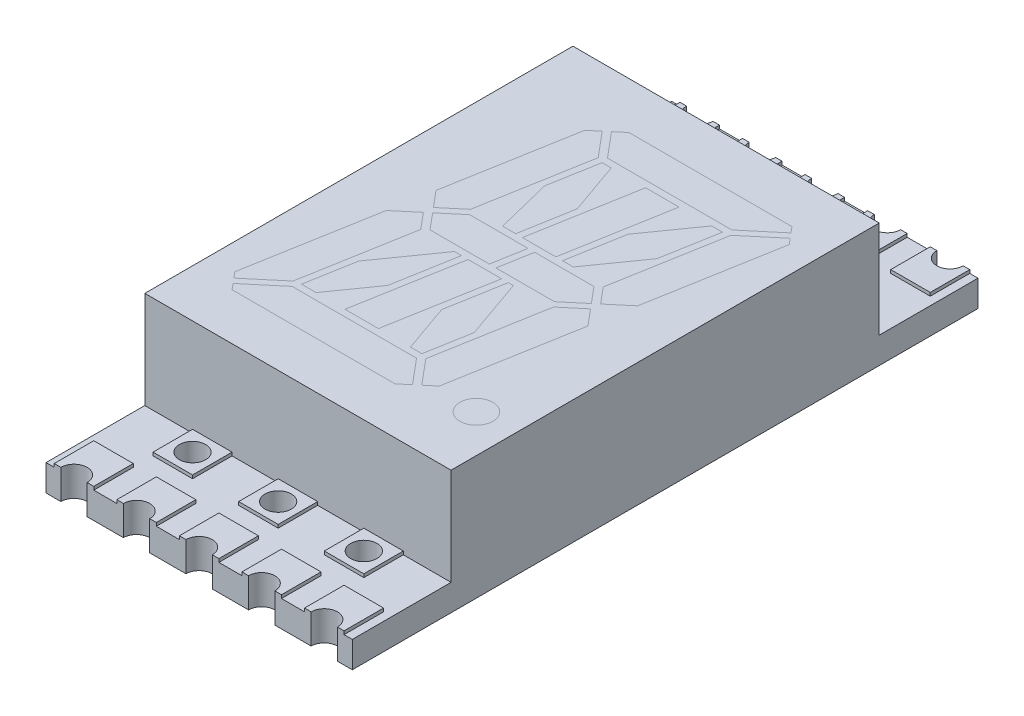
SolidWorks part; units mm, degrees
ref_plane "Спереди" through (0, 0, 0) normal (0, 0, 1) x (1, 0, 0)
ref_plane "Сверху" through (0, 0, 0) normal (0, 1, 0) x (1, 0, 0)
ref_plane "Справа" through (0, 0, 0) normal (1, 0, 0) x (0, 0, -1)
sketch "Эскиз1" plane through (0, 0, 0) normal (0, 1, 0) x (1, 0, 0)
  line L1 (-4.65, 9.5) -> (4.65, 9.5)
  line L2 (-4.65, 9.5) -> (-4.65, -9.5)
  line L3 (-4.65, -9.5) -> (4.65, -9.5)
  line L4 (4.65, 9.5) -> (4.65, -9.5)
  line L5 (-4.65, 9.5) -> (4.65, -9.5) construction
  line L6 (-4.65, -9.5) -> (4.65, 9.5) construction
  point P0 (0, 0)
  dimension "D1" = 9.3
  dimension "D2" = 19
extrude "Бобышка-Вытянуть1" add sketch "Эскиз1" along normal blind 0.8 contours L1 L4 L3 L2
sketch "Эскиз2" plane through (0, 0.8, 0) normal (0, 1, 0) x (1, 0, 0)
  line L0 (4.65, 9.5) -> (4.65, -9.5) construction
  line L1 (-4.65, 6.5) -> (4.65, 6.5)
  line L2 (-4.65, 6.5) -> (-4.65, -6.5)
  line L3 (-4.65, -6.5) -> (4.65, -6.5)
  line L4 (4.65, 6.5) -> (4.65, -6.5)
  line L5 (-4.65, 6.5) -> (4.65, -6.5) construction
  line L6 (-4.65, -6.5) -> (4.65, 6.5) construction
  point P0 (0, 0)
  dimension "D1" = 13
extrude "Бобышка-Вытянуть2" add sketch "Эскиз2" along normal blind 2.95
sketch "Эскиз3" plane through (0, 3.75, 0) normal (0, 1, 0) x (1, 0, 0)
  line L0 (0, 6.5) -> (0, -6.5) construction
  line L1 (4.65, 6.5) -> (-4.65, 6.5) construction
  line L2 (-4.65, -6.5) -> (4.65, -6.5) construction
  line L3 (-2.1505, 5.08) -> (3.942, 5.08) construction
  line L4 (-4.65, 6.5) -> (-4.65, -6.5) construction
  line L5 (-4.65, 0) -> (4.65, 0) construction
  line L6 (4.65, -6.5) -> (4.65, 6.5) construction
  line L7 (-2.1505, 5.08) -> (-3.942, -5.08) construction
  line L8 (3.942, 5.08) -> (2.1505, -5.08) construction
  line L9 (-3.942, -5.08) -> (2.1505, -5.08) construction
  line L10 (-2.1505, 5.08) -> (2.1505, -5.08) construction
  line L11 (-3.942, -5.08) -> (3.942, 5.08) construction
  point P6 (0, 0)
  point P17 (3.5, -4.58)
  dimension "D1" = 10.16
  dimension "D2" = 6
  dimension "D3" = 80
  dimension "D4" = 3.5
  dimension "D5" = 0.5
sketch "Эскиз6" plane through (0, 3.75, 0) normal (0, 1, 0) x (1, 0, 0)
  line L4 (-1.3114, 4.08) -> (-2.7503, -4.08) construction
  line L5 (-1.3114, 4.08) -> (2.7503, 4.08) construction
  line L6 (-2.7503, -4.08) -> (1.3114, -4.08) construction
  line L7 (2.7503, 4.08) -> (1.3114, -4.08) construction
  line L8 (4.65, -6.5) -> (4.65, 6.5)
  line L9 (4.65, 6.5) -> (-4.65, 6.5)
  line L10 (-4.65, 6.5) -> (-4.65, -6.5)
  line L11 (-4.65, -6.5) -> (4.65, -6.5)
  line L12 (4.65, -6.5) -> (4.65, 6.5)
  line L13 (4.65, 6.5) -> (-4.65, 6.5)
  line L14 (-4.65, 6.5) -> (-4.65, -6.5)
  line L15 (-4.65, -6.5) -> (4.65, -6.5)
  line L16 (3.942, 5.08) -> (2.1505, -5.08) construction
  line L17 (-2.1505, 5.08) -> (3.942, 5.08) construction
  line L18 (-3.942, -5.08) -> (2.1505, -5.08) construction
  line L19 (-2.1505, 5.08) -> (-3.942, -5.08) construction
  line L20 (-4.65, 0) -> (4.65, 0) construction
  line L21 (0.8957, 5.08) -> (-0.8957, -5.08) construction
  point P14 (3.0463, 0)
  point P15 (2.0309, 0)
  point P16 (-3.0463, 0)
  point P17 (-2.0309, 0)
  dimension "D2" = 1
  dimension "D3" = 1
  dimension "D4" = 1
  dimension "D5" = 1
  dimension "D1" = 0
sketch "Эскиз8" plane through (0, 3.75, 0) normal (0, 1, 0) x (1, 0, 0)
  line L0 (-1.3114, 4.08) -> (-2.1505, 5.08)
  line L1 (2.7503, 4.08) -> (3.942, 5.08)
  line L2 (2.107, 0.4316) -> (2.9702, -0.4316) construction
  line L3 (1.3114, -4.08) -> (2.1505, -5.08)
  line L4 (1.9222, -0.6164) -> (3.155, 0.6164) construction
  line L5 (-2.7503, -4.08) -> (-3.942, -5.08)
  line L6 (-1.2731, 4.1121) -> (-2.1122, 5.1121) construction
  line L7 (2.7824, 4.0417) -> (3.9742, 5.0417) construction
  line L8 (-2.9702, 0.4316) -> (-2.107, -0.4316) construction
  line L9 (-2.1505, 5.08) -> (3.942, 5.08) construction
  line L10 (-3.155, -0.6164) -> (-1.9222, 0.6164) construction
  line L11 (-2.0309, 0) -> (-3.0463, 0) construction
  line L12 (-2.1505, 5.08) -> (-3.942, -5.08) construction
  line L13 (-2.0309, 0.05) -> (-3.0463, 0.05) construction
  line L14 (2.0309, -0.05) -> (3.0463, -0.05) construction
  line L15 (2.0309, 0) -> (3.0463, 0) construction
  line L16 (1.2731, -4.1121) -> (2.1122, -5.1121) construction
  line L17 (3.942, 5.08) -> (2.1505, -5.08) construction
  line L18 (-2.7824, -4.0417) -> (-3.9742, -5.0417) construction
  line L19 (-1.3497, 4.0479) -> (-2.1888, 5.0479) construction
  line L20 (2.7181, 4.1183) -> (3.9099, 5.1183) construction
  line L21 (-4.65, 0) -> (4.65, 0) construction
  line L22 (-2.0309, -0.05) -> (-3.0463, -0.05) construction
  line L23 (2.0309, 0.05) -> (3.0463, 0.05) construction
  line L24 (1.3497, -4.0479) -> (2.1888, -5.0479) construction
  line L25 (2.7503, 4.08) -> (1.3114, -4.08) construction
  line L26 (-2.7181, -4.1183) -> (-3.9099, -5.1183) construction
  line L27 (-2.2593, 4.463) -> (-1.524, 5.08)
  line L28 (3.2529, 5.08) -> (3.8224, 4.4014)
  line L29 (-3.8224, -4.4014) -> (-3.2529, -5.08)
  line L30 (-1.3114, 4.08) -> (-2.7503, -4.08) construction
  line L31 (1.524, -5.08) -> (2.2593, -4.463)
  line L32 (-3.0055, 0.3963) -> (-2.1423, -0.467) construction
  line L33 (-3.1196, -0.6518) -> (-1.8868, 0.581) construction
  line L34 (2.0716, 0.3963) -> (2.9348, -0.467) construction
  line L35 (1.9575, -0.6518) -> (3.1903, 0.581) construction
  line L36 (-2.9348, 0.467) -> (-2.0716, -0.3963) construction
  line L37 (-3.1903, -0.581) -> (-1.9575, 0.6518) construction
  line L38 (2.1423, 0.467) -> (3.0055, -0.3963) construction
  line L39 (1.8868, -0.581) -> (3.1196, 0.6518) construction
  line L40 (-3.942, -5.08) -> (2.1505, -5.08) construction
  line L41 (-2.3186, 0.5) -> (2.4038, 0.5) construction
  line L43 (2.4038, -0.5) -> (-2.5616, -0.5) construction
  point P19 (2.5386, 0)
  point P21 (-2.5386, 0)
  point P70 (-1.731, 4.58)
  point P73 (3.3461, 4.58)
  point P76 (-3.3461, -4.58)
  point P79 (1.731, -4.58)
  dimension "D3" = 0.25
  dimension "D4" = 0.25
  dimension "D5" = 0.25
  dimension "D6" = 0.25
  dimension "D7" = 45
  dimension "D10" = 1
  dimension "D11" = 0.5
  dimension "D1" = 0.05
  dimension "D8" = 0.05
  dimension "D9" = 0.05
sketch "Эскиз10" plane through (0, 3.75, 0) normal (0, 1, 0) x (1, 0, 0)
  line L0 (-2.9596, 0.4917) -> (-2.5386, 0.0707)
  line L1 (-2.9348, 0.467) -> (-2.0716, -0.3963) construction
  line L2 (-3.1903, -0.581) -> (-1.9575, 0.6518) construction
  line L3 (-2.5386, 0.0707) -> (-1.907, 0.7022)
  line L4 (-1.907, 0.7022) -> (-1.3228, 4.0157)
  line L5 (-1.3497, 4.0479) -> (-2.1888, 5.0479) construction
  line L6 (-1.3228, 4.0157) -> (-1.93, 4.7394)
  line L7 (-2.2593, 4.463) -> (-1.524, 5.08) construction
  line L8 (-1.93, 4.7394) -> (-2.2593, 4.463)
  line L9 (-2.2593, 4.463) -> (-2.9596, 0.4917)
  line L10 (-2.1505, 5.08) -> (-3.942, -5.08) construction
  line L11 (-1.3114, 4.08) -> (-2.7503, -4.08) construction
  line L12 (2.1176, 0.4917) -> (2.5386, 0.0707)
  line L13 (2.5386, 0.0707) -> (3.1701, 0.7022)
  line L14 (3.1701, 0.7022) -> (3.8224, 4.4014)
  line L15 (3.8224, 4.4014) -> (3.5698, 4.7024)
  line L16 (3.5698, 4.7024) -> (2.7368, 4.0034)
  line L17 (2.7368, 4.0034) -> (2.1176, 0.4917)
  line L18 (-3.8224, -4.4014) -> (-3.5698, -4.7024)
  line L19 (2.1423, 0.467) -> (3.0055, -0.3963) construction
  line L20 (3.942, 5.08) -> (2.1505, -5.08) construction
  line L21 (2.7503, 4.08) -> (1.3114, -4.08) construction
  line L22 (1.8868, -0.581) -> (3.1196, 0.6518) construction
  line L23 (3.2529, 5.08) -> (3.8224, 4.4014) construction
  line L24 (2.7824, 4.0417) -> (3.9742, 5.0417) construction
  line L25 (-3.5698, -4.7024) -> (-2.7368, -4.0034)
  line L26 (-2.7368, -4.0034) -> (-2.1176, -0.4917)
  line L27 (-2.1176, -0.4917) -> (-2.5386, -0.0707)
  line L28 (-2.5386, -0.0707) -> (-3.1701, -0.7022)
  line L29 (-3.1701, -0.7022) -> (-3.8224, -4.4014)
  line L30 (-3.0055, 0.3963) -> (-2.1423, -0.467) construction
  line L31 (-3.1196, -0.6518) -> (-1.8868, 0.581) construction
  line L32 (-3.8224, -4.4014) -> (-3.2529, -5.08) construction
  line L33 (-2.7824, -4.0417) -> (-3.9742, -5.0417) construction
  line L34 (-3.2529, -5.08) -> (1.524, -5.08)
  line L35 (1.524, -5.08) -> (1.8534, -4.8037)
  line L36 (1.8534, -4.8037) -> (1.2462, -4.08)
  line L37 (1.2462, -4.08) -> (-2.6725, -4.08)
  line L38 (-2.6725, -4.08) -> (-3.5055, -4.779)
  line L39 (-3.5055, -4.779) -> (-3.2529, -5.08)
  line L40 (-2.7181, -4.1183) -> (-3.9099, -5.1183) construction
  line L41 (-2.7503, -4.08) -> (1.3114, -4.08) construction
  line L42 (-1.524, 5.08) -> (-1.8534, 4.8037)
  line L43 (1.2731, -4.1121) -> (2.1122, -5.1121) construction
  line L44 (1.524, -5.08) -> (2.2593, -4.463) construction
  line L45 (1.3228, -4.0157) -> (1.93, -4.7394)
  line L46 (1.93, -4.7394) -> (2.2593, -4.463)
  line L47 (2.2593, -4.463) -> (2.9596, -0.4917)
  line L48 (2.9596, -0.4917) -> (2.5386, -0.0707)
  line L49 (2.5386, -0.0707) -> (1.907, -0.7022)
  line L50 (1.907, -0.7022) -> (1.3228, -4.0157)
  line L51 (1.9575, -0.6518) -> (3.1903, 0.581) construction
  line L52 (2.0716, 0.3963) -> (2.9348, -0.467) construction
  line L53 (1.3497, -4.0479) -> (2.1888, -5.0479) construction
  line L54 (-1.8534, 4.8037) -> (-1.2462, 4.08)
  line L55 (-1.2462, 4.08) -> (2.6725, 4.08)
  line L56 (2.6725, 4.08) -> (3.5055, 4.779)
  line L57 (3.5055, 4.779) -> (3.2529, 5.08)
  line L58 (3.2529, 5.08) -> (-1.524, 5.08)
  line L59 (-1.2731, 4.1121) -> (-2.1122, 5.1121) construction
  line L60 (-1.3114, 4.08) -> (2.7503, 4.08) construction
  line L61 (2.7181, 4.1183) -> (3.9099, 5.1183) construction
  line L62 (-1.9679, 0.5) -> (-2.4679, 0)
  line L63 (-2.4679, 0) -> (-1.9679, -0.5)
  line L64 (-1.9679, -0.5) -> (1.9373, -0.5306)
  line L65 (1.9373, -0.5306) -> (2.4679, 0)
  line L66 (2.4679, 0) -> (1.9679, 0.5)
  line L67 (1.9679, 0.5) -> (-1.9679, 0.5)
  line L68 (-4.65, 0) -> (4.65, 0) construction
  line L69 (2.4038, -0.5) -> (-2.5616, -0.5) construction
  line L70 (-2.3186, 0.5) -> (2.4038, 0.5) construction
sketch "Эскиз11" plane through (0, 3.75, 0) normal (0, 1, 0) x (1, 0, 0)
  line L0 (2.7503, 4.08) -> (3.942, 5.08) construction
  line L1 (-2.119, -0.5) -> (1.9427, -0.5) construction
  line L2 (-1.3114, 4.08) -> (-2.7503, -4.08) construction
  line L3 (-2.1505, 5.08) -> (-1.3114, 4.08) construction
  line L4 (2.7503, 4.08) -> (1.3114, -4.08) construction
  line L5 (-4.65, 0) -> (4.65, 0) construction
  line L6 (-2.7503, -4.08) -> (-3.6356, -4.8229) construction
  line L7 (-1.9427, 0.5) -> (2.119, 0.5) construction
  line L8 (0.1243, 0.7052) -> (-0.0912, -0.5174) construction
  line L9 (-1.97, 4.7093) -> (-1.3341, 3.9514) construction
  line L10 (2.119, 0.5) -> (3.0121, -0.5643) construction
  line L11 (-2.1505, 5.08) -> (3.942, 5.08) construction
  line L12 (3.942, 5.08) -> (2.1505, -5.08) construction
  line L13 (2.1505, -5.08) -> (-3.942, -5.08) construction
  line L14 (-3.942, -5.08) -> (-2.1505, 5.08) construction
  line L15 (-1.3114, 4.08) -> (2.7503, 4.08) construction
  line L16 (2.7503, 4.08) -> (1.3114, -4.08) construction
  line L17 (1.3114, -4.08) -> (-2.7503, -4.08) construction
  line L18 (-2.7503, -4.08) -> (-1.3114, 4.08) construction
  line L19 (2.0309, 0) -> (3.0463, 0) construction
  line L20 (-2.9581, 0.5) -> (-2.119, -0.5) construction
  line L21 (1.9427, -0.5) -> (3.2257, 0.5766) construction
  line L22 (-3.0463, 0) -> (-2.0309, 0) construction
  line L23 (-3.1344, -0.5) -> (-1.9427, 0.5) construction
  line L24 (1.3114, -4.08) -> (1.8934, -4.7736) construction
  line L25 (-2.9808, 0.3714) -> (-2.1417, -0.6286) construction
  line L26 (-3.1615, -0.6532) -> (-1.7871, 0.5) construction
  line L27 (-2.7233, -3.9268) -> (-3.6999, -4.7463) construction
  line L28 (1.1809, -4.08) -> (1.8168, -4.8379) construction
  line L29 (1.9157, -0.6532) -> (3.29, 0.5) construction
  line L30 (1.9885, 0.5) -> (2.9354, -0.6286) construction
  line L31 (2.7233, 3.9268) -> (3.6999, 4.7463) construction
  line L32 (-1.8168, 4.8379) -> (-1.1809, 4.08) construction
  line L33 (-2.9354, 0.6286) -> (-1.9885, -0.5) construction
  line L34 (-3.1074, -0.3468) -> (-1.9157, 0.6532) construction
  line L35 (-2.5947, -4.08) -> (-3.5713, -4.8995) construction
  line L36 (1.3341, -3.9514) -> (1.97, -4.7093) construction
  line L37 (1.7871, -0.5) -> (3.1615, 0.6532) construction
  line L38 (2.1417, 0.6286) -> (3.0887, -0.5) construction
  line L39 (2.5947, 4.08) -> (3.5713, 4.8995) construction
  line L40 (-2.2586, 4.4672) -> (-1.5282, 5.08) construction
  line L41 (3.4199, 5.08) -> (3.8513, 4.5658) construction
  line L42 (1.5282, -5.08) -> (2.2586, -4.4672) construction
  line L43 (-2.4124, 5.5477) -> (-1.1809, 4.08) construction
  line L44 (-3.8513, -4.5658) -> (-3.4199, -5.08) construction
  line L45 (-2.5656, 5.4191) -> (-1.3341, 3.9514) construction
  line L46 (2.1182, 3.6802) -> (3.8777, 5.1566) construction
  line L47 (2.2468, 3.527) -> (4.0063, 5.0034) construction
  line L48 (-3.7801, -0.9113) -> (-2.007, 0.5766) construction
  line L49 (-3.6516, -1.0645) -> (-1.8784, 0.4234) construction
  line L50 (-3.2753, 0.7224) -> (-2.1956, -0.5643) construction
  line L51 (-3.1221, 0.851) -> (-2.0424, -0.4357) construction
  line L52 (-2.3638, -3.6252) -> (-3.6999, -4.7463) construction
  line L53 (-2.2353, -3.7784) -> (-3.5713, -4.8995) construction
  line L54 (0.6343, -3.1175) -> (1.97, -4.7093) construction
  line L55 (0.4811, -3.246) -> (1.8168, -4.8379) construction
  line L56 (2.0029, 0.794) -> (3.0887, -0.5) construction
  line L57 (1.8496, 0.6655) -> (2.9354, -0.6286) construction
  line L58 (1.4413, -0.7902) -> (3.1615, 0.6532) construction
  line L59 (1.5699, -0.9434) -> (3.29, 0.5) construction
  line L60 (-3.7159, -0.9879) -> (-1.9427, 0.5) construction
  line L61 (-0.0134, 0.5) -> (-0.1897, -0.5) construction
  line L62 (0.1897, 0.5) -> (0.0134, -0.5) construction
  line L63 (0.0259, 0.7226) -> (-0.1897, -0.5) construction
  line L64 (0.2228, 0.6878) -> (0.0073, -0.5347) construction
  line L65 (0.5577, -3.1818) -> (1.8934, -4.7736) construction
  line L66 (2.1825, 3.6036) -> (3.942, 5.08) construction
  line L67 (-2.489, 5.4834) -> (-1.2575, 4.0157) construction
  line L68 (-3.1987, 0.7867) -> (-2.119, -0.5) construction
  line L69 (1.9262, 0.7297) -> (3.0121, -0.5643) construction
  line L70 (1.5056, -0.8668) -> (3.2257, 0.5766) construction
  line L71 (-2.2995, -3.7018) -> (-3.6356, -4.8229) construction
  point P34 (2.5386, 0)
  point P43 (-2.5386, 0)
  point P47 (0.0882, 0.5)
  point P49 (-0.0882, -0.5)
  dimension "D1" = 1
  dimension "D2" = 0.5
  dimension "D5" = 0.4
  dimension "D6" = 0.4
  dimension "D7" = 0.4
  dimension "D8" = 0.4
  dimension "D3" = 0.1
  dimension "D4" = 0.1
sketch "Эскиз13" plane through (0, 3.75, 0) normal (0, 1, 0) x (1, 0, 0)
  line L0 (-2.9354, 0.6286) -> (-2.2586, 4.4672)
  line L1 (-2.2586, 4.4672) -> (-1.97, 4.7093)
  line L2 (-1.97, 4.7093) -> (-1.3341, 3.9514)
  line L3 (-1.3341, 3.9514) -> (-1.9157, 0.6532)
  line L4 (-1.9157, 0.6532) -> (-2.5262, 0.1409)
  line L5 (-2.9354, 0.6286) -> (-1.9885, -0.5) construction
  line L6 (-3.1074, -0.3468) -> (-1.9157, 0.6532) construction
  line L7 (-2.5262, 0.1409) -> (-2.9354, 0.6286)
  line L8 (-3.1615, -0.6532) -> (-2.5509, -0.1409)
  line L9 (-2.9808, 0.3714) -> (-2.1417, -0.6286) construction
  line L10 (-3.1615, -0.6532) -> (-1.7871, 0.5) construction
  line L11 (-2.5509, -0.1409) -> (-2.1417, -0.6286)
  line L12 (-2.1417, -0.6286) -> (-2.7233, -3.9268)
  line L13 (-2.7233, -3.9268) -> (-3.6999, -4.7463)
  line L14 (-3.6999, -4.7463) -> (-3.8513, -4.5658)
  line L15 (-3.8513, -4.5658) -> (-3.1615, -0.6532)
  line L16 (-3.5713, -4.8995) -> (-2.5947, -4.08)
  line L17 (-2.5947, -4.08) -> (1.1809, -4.08)
  line L18 (1.1809, -4.08) -> (1.8168, -4.8379)
  line L19 (1.8168, -4.8379) -> (1.5282, -5.08)
  line L20 (1.5282, -5.08) -> (-3.4199, -5.08)
  line L21 (-3.4199, -5.08) -> (-3.5713, -4.8995)
  line L22 (1.9157, -0.6532) -> (2.5262, -0.1409)
  line L23 (1.9157, -0.6532) -> (3.29, 0.5) construction
  line L24 (1.9885, 0.5) -> (2.9354, -0.6286) construction
  line L25 (2.5262, -0.1409) -> (2.9354, -0.6286)
  line L26 (2.9354, -0.6286) -> (2.2586, -4.4672)
  line L27 (2.2586, -4.4672) -> (1.97, -4.7093)
  line L28 (1.97, -4.7093) -> (1.3341, -3.9514)
  line L29 (1.3341, -3.9514) -> (1.9157, -0.6532)
  line L30 (2.1417, 0.6286) -> (2.5509, 0.1409)
  line L31 (1.7871, -0.5) -> (3.1615, 0.6532) construction
  line L32 (2.1417, 0.6286) -> (3.0887, -0.5) construction
  line L33 (2.5509, 0.1409) -> (3.1615, 0.6532)
  line L34 (3.1615, 0.6532) -> (3.8513, 4.5658)
  line L35 (3.8513, 4.5658) -> (3.6999, 4.7463)
  line L36 (3.6999, 4.7463) -> (2.7233, 3.9268)
  line L37 (2.7233, 3.9268) -> (2.1417, 0.6286)
  line L38 (-1.8168, 4.8379) -> (-1.5282, 5.08)
  line L39 (-1.5282, 5.08) -> (3.4199, 5.08)
  line L40 (3.4199, 5.08) -> (3.5713, 4.8995)
  line L41 (3.5713, 4.8995) -> (2.5947, 4.08)
  line L42 (2.5947, 4.08) -> (-1.1809, 4.08)
  line L43 (-1.1809, 4.08) -> (-1.8168, 4.8379)
  line L44 (-1.9885, -0.5) -> (-0.1897, -0.5)
  line L45 (-0.1897, -0.5) -> (-0.0134, 0.5)
  line L46 (-0.0134, 0.5) -> (-1.7871, 0.5)
  line L47 (-1.7871, 0.5) -> (-2.3977, -0.0123)
  line L48 (-2.3977, -0.0123) -> (-1.9885, -0.5)
  line L49 (0.1897, 0.5) -> (1.9885, 0.5)
  line L50 (1.9885, 0.5) -> (2.3977, 0.0123)
  line L51 (2.3977, 0.0123) -> (1.7871, -0.5)
  line L52 (1.7871, -0.5) -> (0.0134, -0.5)
  line L53 (0.0134, -0.5) -> (0.1897, 0.5)
sketch "Эскиз14" plane through (0, 3.75, 0) normal (0, 1, 0) x (1, 0, 0)
  line L0 (-1.8175, 5.08) -> (1.748, -5.08) construction
  line L1 (0.8957, 5.08) -> (-0.8957, -5.08) construction
  line L2 (-2.1505, 5.08) -> (3.942, 5.08) construction
  line L3 (-3.5295, -5.08) -> (3.6422, 5.08) construction
  line L4 (2.1505, -5.08) -> (-3.942, -5.08) construction
  line L6 (-1.5282, 5.08) -> (3.4199, 5.08) construction
  line L7 (-1.5582, 0.5) -> (1.9885, 0.5) construction
  line L8 (-1.1436, 3.88) -> (-1.7043, 0.7) construction
  line L9 (2.7503, 4.08) -> (1.3114, -4.08) construction
  line L10 (2.1536, 0.6964) -> (2.6916, 3.7472)
  line L11 (2.5119, 3.88) -> (-1.1436, 3.88) construction
  line L12 (-1.3114, 4.08) -> (2.7503, 4.08) construction
  line L13 (2.1536, 4.08) -> (-1.1436, 4.08) construction
  line L14 (1.9512, 0.7) -> (2.5119, 3.88) construction
  line L15 (-2.7503, -4.08) -> (-1.3114, 4.08) construction
  line L16 (-1.3701, 3.7472) -> (-1.9013, 0.7347) construction
  line L17 (-1.9427, 0.5) -> (2.119, 0.5) construction
  line L18 (-1.7043, 0.7) -> (1.9885, 0.7) construction
  line L19 (1.4695, -0.7) -> (-1.6378, -0.7) construction
  line L20 (1.3114, -4.08) -> (-2.7503, -4.08) construction
  line L21 (1.3569, -3.822) -> (1.8699, -0.9131) construction
  line L22 (-1.9949, -0.9478) -> (-2.5119, -3.88) construction
  line L23 (1.4695, -0.5) -> (-1.6378, -0.5) construction
  line L24 (-2.5119, -3.88) -> (1.1436, -3.88) construction
  line L25 (-2.1919, -0.9131) -> (-2.6711, -3.6308) construction
  line L26 (-2.4334, -4.08) -> (0.7693, -4.08) construction
  line L27 (-2.119, -0.5) -> (1.9427, -0.5) construction
  line L28 (1.1436, -3.88) -> (1.6729, -0.8783) construction
  line L29 (1.9567, 0.7311) -> (2.4946, 3.7819) construction
  line L30 (2.1536, 3.88) -> (-1.1436, 3.88) construction
  line L31 (-1.1732, 3.7125) -> (-1.7043, 0.7) construction
  line L32 (-1.5582, 0.7) -> (1.9885, 0.7) construction
  line L33 (1.16, -3.7873) -> (1.6729, -0.8783) construction
  line L34 (-2.4334, -3.88) -> (0.7693, -3.88) construction
  line L35 (-1.9949, -0.9478) -> (-2.4741, -3.6655) construction
  dimension "D1" = 0.2
  dimension "D2" = 0.2
sketch "Эскиз16" plane through (0, 3.75, 0) normal (0, 1, 0) x (1, 0, 0)
  line L0 (-0.1234, -0.7) -> (-0.6841, -3.88) construction
  line L2 (-2.5119, -3.88) -> (1.1436, -3.88) construction
  line L3 (0.8957, 5.08) -> (-0.8957, -5.08) construction
  line L4 (1.4695, -0.7) -> (-1.6378, -0.7) construction
  line L5 (0.6841, 3.88) -> (0.1234, 0.7) construction
  line L6 (2.5119, 3.88) -> (-1.1436, 3.88) construction
  line L7 (-1.7043, 0.7) -> (1.9885, 0.7) construction
  line L8 (0.1764, 3.88) -> (-0.3843, 0.7) construction
  line L9 (-0.6311, -0.7) -> (-1.1766, -3.7932) construction
  line L10 (1.1919, 3.88) -> (0.6311, 0.7) construction
  line L11 (0.3843, -0.7) -> (-0.1917, -3.9668) construction
  line L12 (0.1917, 3.9668) -> (-0.369, 0.7868) construction
  line L13 (1.1766, 3.7932) -> (0.6158, 0.6132) construction
  line L14 (-0.6158, -0.6132) -> (-1.1766, -3.7932) construction
  line L15 (0.369, -0.7868) -> (-0.1917, -3.9668) construction
  dimension "D1" = 0.5
  dimension "D2" = 0.5
sketch "Эскиз17" plane through (0, 3.75, 0) normal (0, 1, 0) x (1, 0, 0)
  line L0 (-0.3843, 0.7) -> (0.6311, 0.7)
  line L1 (-0.3843, 0.7) -> (0.1764, 3.88)
  line L2 (0.6311, 0.7) -> (1.1919, 3.88)
  line L3 (0.1764, 3.88) -> (1.1919, 3.88)
  line L4 (-0.6311, -0.7) -> (-1.1919, -3.88)
  line L5 (-0.6311, -0.7) -> (0.3843, -0.7)
  line L6 (-1.1919, -3.88) -> (-0.1764, -3.88)
  line L7 (0.3843, -0.7) -> (-0.1764, -3.88)
  line L8 (-2.5119, -3.88) -> (1.1436, -3.88) construction
  line L9 (0.3843, -0.7) -> (-0.1917, -3.9668) construction
sketch "Эскиз19" plane through (0, 3.75, 0) normal (0, 1, 0) x (1, 0, 0)
  line L0 (0.1764, 3.88) -> (-1.1919, -3.88) construction
  line L3 (-0.1764, -3.88) -> (1.1919, 3.88) construction
  line L4 (1.1919, 3.88) -> (2.5119, 3.88) construction
  line L5 (2.5119, 3.88) -> (1.1436, -3.88) construction
  line L6 (0.0205, -3.9147) -> (1.3888, 3.8453) construction
  line L7 (-0.0205, 3.9147) -> (-1.3888, -3.8453) construction
  line L8 (-2.5119, -3.88) -> (-1.1436, 3.88) construction
  line L9 (-1.5119, 4.2093) -> (1.4114, -4.1208) construction
  line L10 (-1.8175, 5.08) -> (1.748, -5.08) construction
  line L11 (-2.3963, -4.3417) -> (3.4428, 3.9305) construction
  line L12 (-1.9837, 4.0437) -> (0.9396, -4.2864) construction
  line L13 (-3.5295, -5.08) -> (3.6422, 5.08) construction
  line L14 (-2.8048, -4.0533) -> (3.0343, 4.2188) construction
  line L15 (-3.2133, -3.765) -> (2.6258, 4.5072) construction
  line L16 (-1.0401, 4.3748) -> (1.8832, -3.9553) construction
  dimension "D1" = 0.2
  dimension "D2" = 0.5
  dimension "D3" = 0.5
sketch "Эскиз21" plane through (0, 3.75, 0) normal (0, 1, 0) x (1, 0, 0)
  line L0 (-2.2513, -2.4022) -> (-2.5119, -3.88)
  line L1 (-1.9949, -0.9478) -> (-2.5119, -3.88) construction
  line L2 (-2.5119, -3.88) -> (-2.0704, -3.88)
  line L3 (-2.5119, -3.88) -> (1.1436, -3.88) construction
  line L4 (-2.0704, -3.88) -> (-1.17, -2.6044)
  line L5 (-0.0205, 3.9147) -> (-1.3888, -3.8453) construction
  line L6 (-1.17, -2.6044) -> (-0.8342, -0.7)
  line L7 (1.4695, -0.7) -> (-1.6378, -0.7) construction
  line L8 (-0.8342, -0.7) -> (-1.0498, -0.7)
  line L9 (-1.0498, -0.7) -> (-2.2513, -2.4022)
  line L10 (-3.2133, -3.765) -> (2.6258, 4.5072) construction
  line L11 (-2.3963, -4.3417) -> (3.4428, 3.9305) construction
  line L12 (0.5874, -0.7) -> (0.7408, -0.7)
  line L13 (-1.0401, 4.3748) -> (1.8832, -3.9553) construction
  line L14 (0.7408, -0.7) -> (1.3821, -2.5274)
  line L15 (1.1436, -3.88) -> (1.6729, -0.8783) construction
  line L16 (1.3821, -2.5274) -> (1.1436, -3.88)
  line L17 (1.1436, -3.88) -> (0.797, -3.88)
  line L18 (0.797, -3.88) -> (0.2843, -2.419)
  line L19 (0.0205, -3.9147) -> (1.3888, 3.8453) construction
  line L20 (-1.9837, 4.0437) -> (0.9396, -4.2864) construction
  line L21 (0.2843, -2.419) -> (0.5874, -0.7)
  line L22 (2.1831, 3.88) -> (2.5119, 3.88)
  line L23 (2.5119, 3.88) -> (-1.1436, 3.88) construction
  line L24 (2.5119, 3.88) -> (2.2138, 2.1894)
  line L25 (1.9512, 0.7) -> (2.5119, 3.88) construction
  line L26 (2.2138, 2.1894) -> (1.1625, 0.7)
  line L27 (-1.7043, 0.7) -> (1.9885, 0.7) construction
  line L28 (1.1625, 0.7) -> (0.8342, 0.7)
  line L29 (0.8342, 0.7) -> (1.1325, 2.3916)
  line L30 (1.1325, 2.3916) -> (2.1831, 3.88)
  line L31 (-0.9849, 0.7) -> (-0.5874, 0.7)
  line L32 (-0.5874, 0.7) -> (-0.3075, 2.2872)
  line L33 (-0.3075, 2.2872) -> (-0.8664, 3.88)
  line L34 (-0.8664, 3.88) -> (-1.1436, 3.88)
  line L35 (-1.1436, 3.88) -> (-1.4053, 2.3957)
  line L36 (-1.1436, 3.88) -> (-1.7043, 0.7) construction
  line L37 (-1.4053, 2.3957) -> (-0.9849, 0.7)
extrude "Вырез-Вытянуть1" cut sketch "Эскиз21" against normal blind 0.2
extrude "Вырез-Вытянуть2" cut sketch "Эскиз17" against normal blind 0.2
extrude "Вырез-Вытянуть3" cut sketch "Эскиз13" against normal blind 0.2
sketch "Эскиз22" plane through (0, 3.75, 0) normal (0, 1, 0) x (1, 0, 0)
  circle A0 centre (3.5, -4.58) radius 0.5
extrude "Вырез-Вытянуть4" cut sketch "Эскиз22" against normal blind 0.2
sketch "Эскиз24" plane through (0, 0.8, 0) normal (0, 1, 0) x (1, 0, 0)
  line L0 (0, 9.5) -> (0, -9.5) construction
  line L1 (-4.65, 9.5) -> (4.65, 9.5) construction
  line L2 (-4.65, -9.5) -> (4.65, -9.5) construction
  line L3 (-4.4, 8.3) -> (-3.2, 8.3)
  line L8 (-4.4, 8.3) -> (-4.4, 9.5)
  line L9 (-4.4, 9.5) -> (-3.2, 9.5)
  line L10 (-0.6, 6.5) -> (0.6, 6.5)
  line L11 (-0.6, 6.5) -> (-0.6, 7.7)
  line L12 (-0.6, 7.7) -> (0.6, 7.7)
  line L13 (0.6, 6.5) -> (0.6, 7.7)
  line L14 (-0.6, 6.5) -> (0.6, 7.7) construction
  line L15 (-0.6, 7.7) -> (0.6, 6.5) construction
  line L16 (4.65, 6.5) -> (-4.65, 6.5) construction
  line L17 (-3.2, 6.5) -> (-2, 6.5)
  line L18 (-3.2, 6.5) -> (-3.2, 7.7)
  line L19 (-3.2, 7.7) -> (-2, 7.7)
  line L20 (-2, 6.5) -> (-2, 7.7)
  line L21 (-3.2, 6.5) -> (-2, 7.7) construction
  line L22 (-3.2, 7.7) -> (-2, 6.5) construction
  line L27 (-3.2, 8.3) -> (-3.2, 9.5)
  line L28 (-4.4, 8.3) -> (-3.2, 9.5) construction
  line L29 (2, 6.5) -> (3.2, 6.5)
  line L30 (2, 6.5) -> (2, 7.7)
  line L31 (2, 7.7) -> (3.2, 7.7)
  line L32 (3.2, 6.5) -> (3.2, 7.7)
  line L33 (2, 6.5) -> (3.2, 7.7) construction
  line L34 (2, 7.7) -> (3.2, 6.5) construction
  line L35 (-4.4, 9.5) -> (-3.2, 8.3) construction
  line L36 (-2.5, 8.3) -> (-1.3, 8.3)
  line L37 (-2.5, 8.3) -> (-2.5, 9.5)
  line L38 (-2.5, 9.5) -> (-1.3, 9.5)
  line L39 (-1.3, 8.3) -> (-1.3, 9.5)
  line L40 (-2.5, 8.3) -> (-1.3, 9.5) construction
  line L41 (-2.5, 9.5) -> (-1.3, 8.3) construction
  line L42 (-0.6, 8.3) -> (0.6, 8.3)
  line L43 (-0.6, 8.3) -> (-0.6, 9.5)
  line L44 (-0.6, 9.5) -> (0.6, 9.5)
  line L45 (0.6, 8.3) -> (0.6, 9.5)
  line L46 (-0.6, 8.3) -> (0.6, 9.5) construction
  line L47 (-0.6, 9.5) -> (0.6, 8.3) construction
  line L48 (1.3, 8.3) -> (2.5, 8.3)
  line L49 (1.3, 8.3) -> (1.3, 9.5)
  line L50 (1.3, 9.5) -> (2.5, 9.5)
  line L51 (2.5, 8.3) -> (2.5, 9.5)
  line L52 (1.3, 8.3) -> (2.5, 9.5) construction
  line L53 (1.3, 9.5) -> (2.5, 8.3) construction
  line L54 (3.2, 8.3) -> (4.4, 8.3)
  line L55 (3.2, 8.3) -> (3.2, 9.5)
  line L56 (3.2, 9.5) -> (4.4, 9.5)
  line L57 (4.4, 8.3) -> (4.4, 9.5)
  line L58 (3.2, 8.3) -> (4.4, 9.5) construction
  line L59 (3.2, 9.5) -> (4.4, 8.3) construction
  line L60 (4.65, 0) -> (-4.65, 0) construction
  line L61 (3.2, -9.5) -> (4.4, -8.3) construction
  line L62 (3.2, -8.3) -> (4.4, -9.5) construction
  line L63 (1.3, -9.5) -> (2.5, -8.3) construction
  line L64 (1.3, -8.3) -> (2.5, -9.5) construction
  line L65 (-0.6, -9.5) -> (0.6, -8.3) construction
  line L66 (-0.6, -8.3) -> (0.6, -9.5) construction
  line L67 (-2.5, -9.5) -> (-1.3, -8.3) construction
  line L68 (-2.5, -8.3) -> (-1.3, -9.5) construction
  line L69 (-4.4, -9.5) -> (-3.2, -8.3) construction
  line L70 (2, -7.7) -> (3.2, -6.5) construction
  line L71 (2, -6.5) -> (3.2, -7.7) construction
  line L72 (-4.4, -8.3) -> (-3.2, -9.5) construction
  line L73 (-3.2, -7.7) -> (-2, -6.5) construction
  line L74 (-3.2, -6.5) -> (-2, -7.7) construction
  line L75 (-0.6, -7.7) -> (0.6, -6.5) construction
  line L76 (-0.6, -6.5) -> (0.6, -7.7) construction
  line L77 (4.4, -8.3) -> (4.4, -9.5)
  line L78 (3.2, -9.5) -> (4.4, -9.5)
  line L79 (3.2, -8.3) -> (3.2, -9.5)
  line L80 (3.2, -8.3) -> (4.4, -8.3)
  line L81 (2.5, -8.3) -> (2.5, -9.5)
  line L82 (1.3, -9.5) -> (2.5, -9.5)
  line L83 (1.3, -8.3) -> (1.3, -9.5)
  line L84 (1.3, -8.3) -> (2.5, -8.3)
  line L85 (0.6, -8.3) -> (0.6, -9.5)
  line L86 (-0.6, -9.5) -> (0.6, -9.5)
  line L87 (-0.6, -8.3) -> (-0.6, -9.5)
  line L88 (-0.6, -8.3) -> (0.6, -8.3)
  line L89 (-1.3, -8.3) -> (-1.3, -9.5)
  line L90 (-2.5, -9.5) -> (-1.3, -9.5)
  line L91 (-2.5, -8.3) -> (-2.5, -9.5)
  line L92 (-2.5, -8.3) -> (-1.3, -8.3)
  line L93 (3.2, -6.5) -> (3.2, -7.7)
  line L94 (2, -7.7) -> (3.2, -7.7)
  line L95 (2, -6.5) -> (2, -7.7)
  line L96 (2, -6.5) -> (3.2, -6.5)
  line L97 (-3.2, -8.3) -> (-3.2, -9.5)
  line L98 (-2, -6.5) -> (-2, -7.7)
  line L99 (-3.2, -7.7) -> (-2, -7.7)
  line L100 (-3.2, -6.5) -> (-3.2, -7.7)
  line L101 (-3.2, -6.5) -> (-2, -6.5)
  line L102 (0.6, -6.5) -> (0.6, -7.7)
  line L103 (-0.6, -7.7) -> (0.6, -7.7)
  line L104 (-0.6, -6.5) -> (-0.6, -7.7)
  line L105 (-0.6, -6.5) -> (0.6, -6.5)
  line L106 (-4.4, -9.5) -> (-3.2, -9.5)
  line L107 (-4.4, -8.3) -> (-4.4, -9.5)
  line L108 (-4.4, -8.3) -> (-3.2, -8.3)
  point P13 (0, 7.1)
  point P21 (-2.6, 7.1)
  point P28 (-1.9, 8.9)
  point P31 (-3.8, 8.9)
  point P32 (2.6, 7.1)
  point P44 (0, 8.9)
  point P49 (1.9, 8.9)
  point P54 (3.8, 8.9)
  point P102 (3.8, -8.9)
  point P103 (1.9, -8.9)
  point P104 (0, -8.9)
  point P105 (2.6, -7.1)
  point P106 (-3.8, -8.9)
  point P107 (-1.9, -8.9)
  point P108 (-2.6, -7.1)
  point P109 (0, -7.1)
  dimension "D3" = 1.2
  dimension "D4" = 1.2
  dimension "D5" = 2.6
  dimension "D7" = 5
extrude "Бобышка-Вытянуть3" add sketch "Эскиз24" along normal blind 0.1
sketch "Эскиз26" plane through (0, 0.9, -0.9) normal (0, -1, 0) x (1, 0, 0)
  line L14 (-3.2, -6.2) -> (3.2, -6.2) construction
  line L15 (-3.2, -6.8) -> (-3.2, -5.6) construction
  line L21 (3.2, -5.6) -> (3.2, -6.8) construction
  line L22 (-4.65, 0.9) -> (4.65, 0.9) construction
  line L28 (-3.2, -8.6) -> (-4.4, -8.6) construction
  line L33 (-2, -6.8) -> (-3.2, -6.8) construction
  circle A12 centre (-2.6, -6.2) radius 0.4
  circle A13 centre (-3.8, -8.6) radius 0.4
  circle A14 centre (-1.9, -8.6) radius 0.4
  circle A15 centre (0, -8.6) radius 0.4
  circle A16 centre (1.9, -8.6) radius 0.4
  circle A17 centre (3.8, -8.6) radius 0.4
  circle A18 centre (0, -6.2) radius 0.4
  circle A19 centre (2.6, -6.2) radius 0.4
  circle A20 centre (2.6, 8) radius 0.4
  circle A21 centre (0, 8) radius 0.4
  circle A22 centre (-2.6, 8) radius 0.4
  circle A23 centre (3.8, 10.4) radius 0.4
  circle A24 centre (1.9, 10.4) radius 0.4
  circle A25 centre (0, 10.4) radius 0.4
  circle A26 centre (-1.9, 10.4) radius 0.4
  circle A27 centre (-3.8, 10.4) radius 0.4
  point P1 (3.5403, 10.3897)
  point P2 (1.6393, 10.3897)
  point P3 (-0.2618, 10.3897)
  point P20 (-2.6, -6.8)
  dimension "D1" = 3
  dimension "D2" = 5
extrude "Вырез-Вытянуть5" cut sketch "Эскиз26" against normal through all both and the other way through all
extrude "Бобышка-Вытянуть5" add sketch "Эскиз21<5>" against normal up to surface (0.2 mm away) separate body up to face at (-0.8825, 3.55, -2.3072)
sketch "Эскиз21<5>" plane through (0, 3.75, 0) normal (0, 1, 0) x (1, 0, 0) same geometry as "Эскиз21"
extrude "Бобышка-Вытянуть6" add sketch "Эскиз17<2>" against normal up to surface (0.2 mm away) separate body up to face at (0.4038, 3.55, -2.29)
sketch "Эскиз17<2>" plane through (0, 3.75, 0) normal (0, 1, 0) x (1, 0, 0) same geometry as "Эскиз17"
extrude "Бобышка-Вытянуть7" add sketch "Эскиз13<3>" against normal up to surface (0.2 mm away) separate body up to face at (-2.1567, 3.55, -2.4251)
sketch "Эскиз13<3>" plane through (0, 3.75, 0) normal (0, 1, 0) x (1, 0, 0) same geometry as "Эскиз13"
extrude "Бобышка-Вытянуть8" add sketch "Эскиз22<2>" against normal up to surface (0.2 mm away) separate body up to face at (3.5, 3.55, 5.08)
sketch "Эскиз22<2>" plane through (0, 3.75, 0) normal (0, 1, 0) x (1, 0, 0) same geometry as "Эскиз22"
equation "\"D4@Эскиз8\"=\"D3@Эскиз8\""
equation "\"D6@Эскиз8\"=\"D3@Эскиз8\""
equation "\"D5@Эскиз8\"=\"D3@Эскиз8\""
equation "\"D6@Эскиз11\"=\"D5@Эскиз11\""
equation "\"D7@Эскиз11\"=\"D5@Эскиз11\""
equation "\"D8@Эскиз11\"=\"D5@Эскиз11\""
